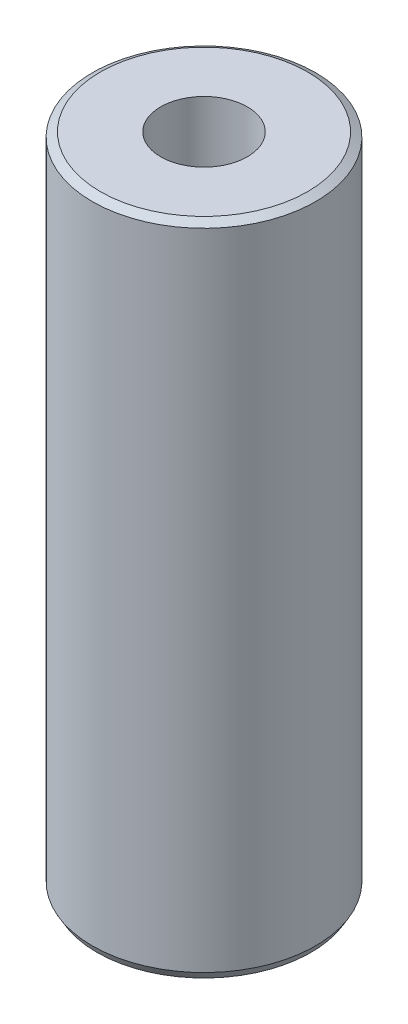
SolidWorks part; units mm, degrees
ref_plane "Front Plane" through (0, 0, 0) normal (0, 0, 1) x (1, 0, 0)
ref_plane "Top Plane" through (0, 0, 0) normal (0, 1, 0) x (1, 0, 0)
ref_plane "Right Plane" through (0, 0, 0) normal (1, 0, 0) x (0, 0, -1)
sketch "Sketch1" plane through (0, 0, 0) normal (0, 1, 0) x (1, 0, 0)
  circle A0 centre (0, 0) radius 5
  dimension "SHAFT_OD" = 10
extrude "Boss-Extrude1" add sketch "Sketch1" along normal blind 29.4263
sketch "Sketch2" plane through (0, 0, 0) normal (0, 1, 0) x (1, 0, 0)
  circle A0 centre (0, 0) radius 1.9404
  dimension "BORE_D" = 3.8808
extrude "Cut-Extrude1" cut sketch "Sketch2" along normal through all
chamfer "Chamfer1" distance 0.2072 angle 60 2 edges at (0, 29.4263, 5) (0, 0, 5) first distance on face at (0, 29.4263, 5) first distance on face at (0, 0, 1.9404)
